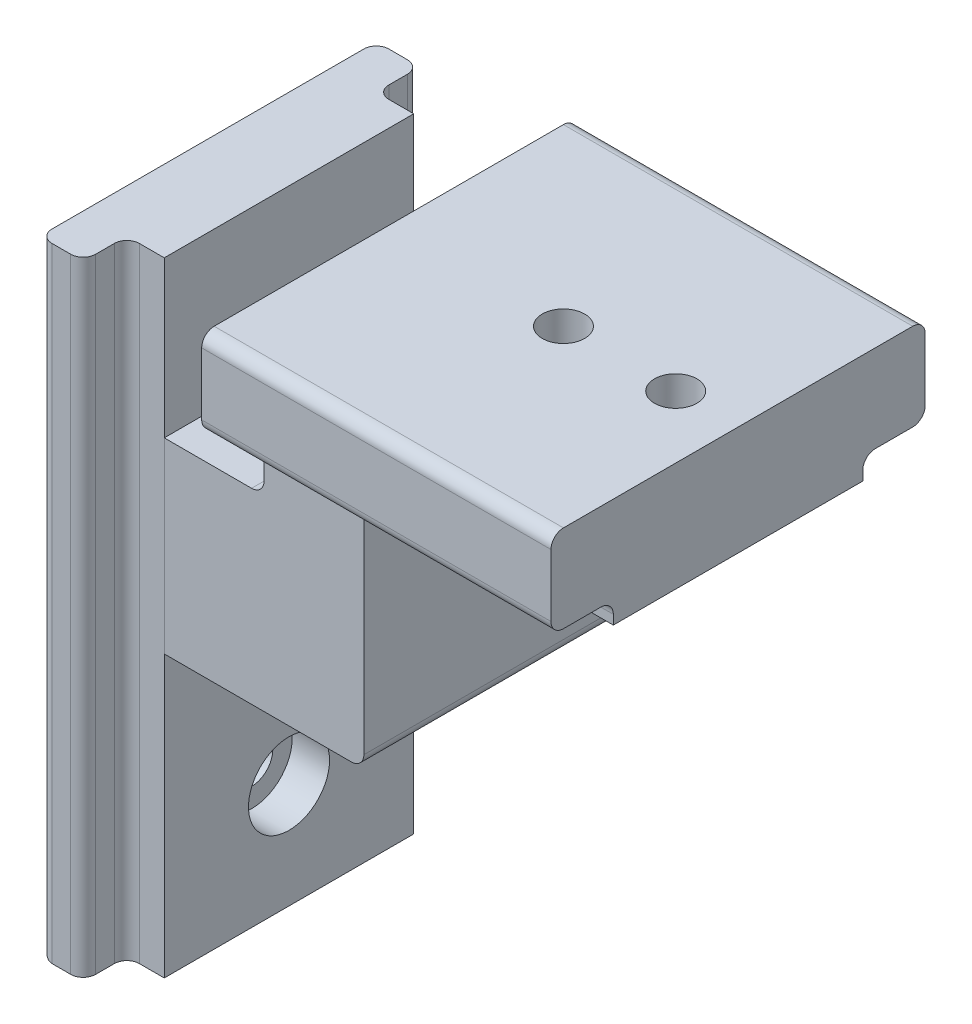
SolidWorks part; units mm, degrees
ref_plane "Front Plane" through (0, 0, 0) normal (0, 0, 1) x (1, 0, 0)
ref_plane "Top Plane" through (0, 0, 0) normal (0, 1, 0) x (1, 0, 0)
ref_plane "Right Plane" through (0, 0, 0) normal (1, 0, 0) x (0, 0, -1)
sketch "Sketch1" plane through (0, 0, 0) normal (0, 0, 1) x (1, 0, 0)
  line L0 (16, -7.5) -> (0, -7.5)
  line L1 (0, -7.5) -> (0, 7.5)
  line L2 (0, 7.5) -> (8, 7.5)
  line L3 (8, 7.5) -> (8, 12.5)
  line L4 (8, 12.5) -> (16, 12.5)
  line L5 (16, 12.5) -> (16, -7.5)
  point P8 (0, 0)
  dimension "D1" = 15
  dimension "D2" = 20
  dimension "D3" = 8
  dimension "D4" = 16
extrude "Boss-Extrude1" add sketch "Sketch1" along normal mid plane 20
sketch "Sketch2" plane through (0, 0, 0) normal (0, 1, 0) x (1, 0, 0)
  line L0 (-3, 13.5) -> (-6.5, 13.5)
  line L1 (-6.5, 13.5) -> (-6.5, -13.5)
  line L2 (-6.5, -13.5) -> (-3, -13.5)
  line L3 (-3, -13.5) -> (-3, -10)
  line L5 (-3, 10) -> (0, 10)
  line L7 (0, 10) -> (0, -10)
  line L9 (0, -10) -> (-3, -10)
  line L10 (-3, 10) -> (-3, 13.5)
  point P11 (-6.5, 0)
  dimension "D1" = 3.5
  dimension "D2" = 27
  dimension "D3" = 3
extrude "Boss-Extrude2" add sketch "Sketch2" along normal blind 20 and the other way blind 30
sketch "Sketch7" plane through (8, 0, 0) normal (-1, 0, 0) x (0, 0, 1)
  line L0 (-10, 12.5) -> (-10, 14.25)
  line L1 (-10, 14.25) -> (-15, 14.25)
  line L2 (-15, 14.25) -> (-15, 21.25)
  line L3 (-15, 21.25) -> (15, 21.25)
  line L4 (15, 21.25) -> (15, 14.25)
  line L5 (15, 14.25) -> (10, 14.25)
  line L6 (10, 14.25) -> (10, 12.5)
  line L7 (-10, 12.5) -> (10, 12.5)
  point P3 (0, 12.5)
  point P10 (0, 21.25)
  dimension "D1" = 30
  dimension "D2" = 1.75
  dimension "D3" = 7
extrude "Boss-Extrude4" add sketch "Sketch7" along normal up to surface and the other way blind 20 from surface up to face at (8, 10, 0) starting at face at (16, 2.5, 0)
hole_wizard "CBORE for M3 SHCS10" positions "Sketch8" profile "Sketch10" counterbore size "M3" standard "ANSI Metric" end condition through all
sketch "Sketch8" plane through (0, 12.5, 0) normal (0, -1, 0) x (-1, 0, 0)
  line L0 (-36, 10) -> (-36, -10) construction
  point P0 (-22, 0)
  point P2 (-31, 0)
  dimension "D1" = 9
  dimension "D2" = 5
sketch "Sketch10" plane through (22, 12.5, 0) normal (1, 0, 0) x (0, 0, -1)
  line L0 (0, 0) -> (0, 8.75)
  line L1 (0, 8.75) -> (1.7, 8.75)
  line L3 (1.7, 8.75) -> (1.7, 3)
  line L4 (1.7, 3) -> (3.25, 3)
  line L5 (3.25, 3) -> (3.25, 0)
  line L7 (3.25, 0) -> (0, 0)
  line L11 (0, -6.35) -> (0, 107.95) construction
  dimension "Thru Hole Dia." = 3.4
  dimension "Thru Hole Depth" = 8.75
  dimension "C'Bore Dia." = 6.5
  dimension "C'Bore Depth" = 3
hole_wizard "CBORE for M3 SHCS11" positions "Sketch11" profile "Sketch12" counterbore size "M3" standard "ANSI Metric" end condition through all
sketch "Sketch11" plane through (0, 0, 0) normal (1, 0, 0) x (0, 0, -1)
  line L0 (-10, -7.5) -> (10, -7.5) construction
  point P0 (0, -12.5)
  point P2 (0, -21.5)
  dimension "D1" = 5
  dimension "D2" = 9
sketch "Sketch12" plane through (0, -12.5, 0) normal (0, 1, 0) x (0, 0, -1)
  line L0 (0, 0) -> (0, 6.5)
  line L1 (0, 6.5) -> (1.7, 6.5)
  line L3 (1.7, 6.5) -> (1.7, 3)
  line L4 (1.7, 3) -> (3.25, 3)
  line L5 (3.25, 3) -> (3.25, 0)
  line L7 (3.25, 0) -> (0, 0)
  line L11 (0, -6.35) -> (0, 107.95) construction
  dimension "Thru Hole Dia." = 3.4
  dimension "Thru Hole Depth" = 6.5
  dimension "C'Bore Dia." = 6.5
  dimension "C'Bore Depth" = 3
hole_wizard "CBORE for M3 SHCS13" positions "Sketch13" profile "Sketch15" counterbore size "M3" standard "ANSI Metric"
sketch "Sketch13" plane through (-6.5, 0, 0) normal (-1, 0, 0) x (0, 0, 1)
  line L0 (0, 0) -> (0, 7.5) construction
  line L2 (-10, 20) -> (-10, -30) construction
  line L9 (-10, 7.5) -> (10, 7.5) construction
  point P0 (-5, 0)
  point P2 (5, 0)
  dimension "D1" = 5
sketch "Sketch15" plane through (-6.5, 0, -5) normal (0, 1, 0) x (0, 0, 1)
  line L0 (0, 0) -> (0, 20)
  line L1 (0, 20) -> (1.7, 18.9785)
  line L2 (1.7, 18.9785) -> (1.7, 3)
  line L3 (1.7, 3) -> (3.25, 3)
  line L4 (3.25, 3) -> (3.25, 0)
  line L5 (3.25, 0) -> (0, 0)
  line L10 (0, 20) -> (-1.7, 18.9785) construction
  line L11 (0, -6.35) -> (0, 107.95) construction
  dimension "Hole Dia." = 3.4
  dimension "Hole Depth" = 20
  dimension "C'Bore Dia." = 6.5
  dimension "C'Bore Depth" = 3
  dimension "Drill Angle" = 118
fillet "Fillet1" radius 1 15 edges at (22, 14.25, -10) (22, 14.25, -15) (22, 21.25, -15) (22, 21.25, 15) (22, 14.25, 15) (22, 14.25, 10) (-6.5, -5, 13.5) (-6.5, -30, 0) (-3, -5, -10) (-3, -5, -13.5) (-6.5, -5, -13.5) (-3, -5, 13.5) (-3, -5, 10) (8, 7.5, 0) (16, -7.5, 0) tangent propagation no
split "Split1" trim tools "Right Plane" bodies to split 113 resulting bodies 114 115
